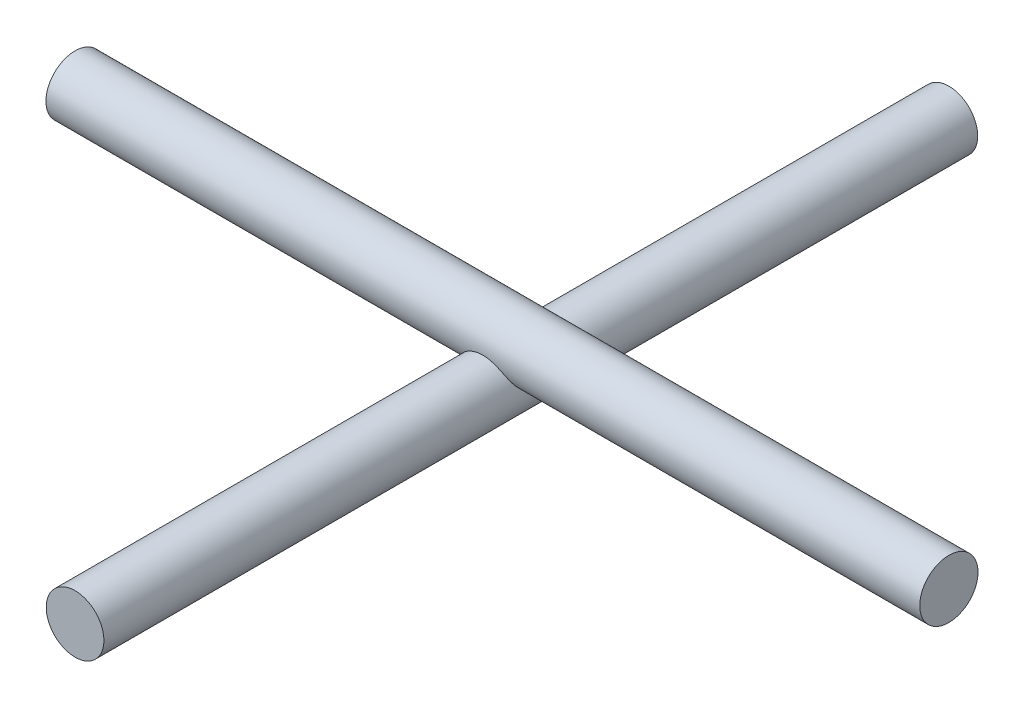
SolidWorks part; units mm, degrees
ref_plane "Front Plane" through (0, 0, 0) normal (0, 0, 1) x (1, 0, 0)
ref_plane "Top Plane" through (0, 0, 0) normal (0, 1, 0) x (1, 0, 0)
ref_plane "Right Plane" through (0, 0, 0) normal (1, 0, 0) x (0, 0, -1)
sketch "Sketch2" plane through (0, 0, 0) normal (0, 0, 1) x (1, 0, 0)
  circle A0 centre (0, 0) radius 2.475
  dimension "D1" = 4.95
extrude "Boss-Extrude1" add sketch "Sketch2" along normal blind 37.5 and the other way blind 37.5
sketch "Sketch3" plane through (0, 0, 0) normal (1, 0, 0) x (0, 0, -1)
  circle A0 centre (0, 2.6) radius 2.5
  dimension "D1" = 5
  dimension "D2" = 2.6
extrude "Boss-Extrude2" add sketch "Sketch3" along normal blind 37.5 and the other way blind 37.5
